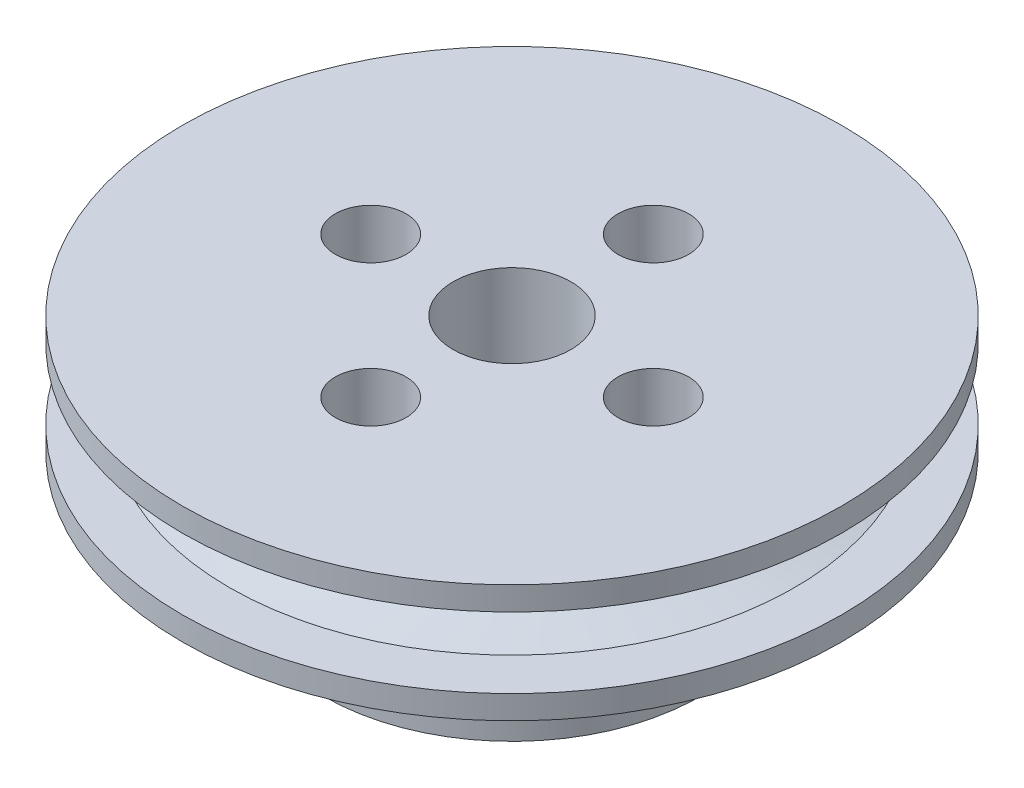
SolidWorks part; units mm, degrees
material "PET"
ref_plane "前视基准面" through (0, 0, 0) normal (0, 0, 1) x (1, 0, 0)
ref_plane "上视基准面" through (0, 0, 0) normal (0, 1, 0) x (1, 0, 0)
ref_plane "右视基准面" through (0, 0, 0) normal (1, 0, 0) x (0, 0, -1)
sketch "草图1" plane through (0, 0, 0) normal (0, 1, 0) x (1, 0, 0)
  circle A0 centre (0, 0) radius 8
  dimension "D1" = 16
extrude "凸台-拉伸1" add sketch "草图1" along normal blind 5
sketch "草图3" plane through (0, 0, 0) normal (0, 0, 1) x (1, 0, 0)
  line L0 (2.5, 5) -> (12, 5)
  line L1 (8, 5) -> (-8, 5) construction
  line L3 (12, 10) -> (2.5, 10)
  line L4 (0, 11) -> (0, 5) construction
  line L5 (12, 9) -> (12, 10)
  line L6 (12, 6) -> (12, 5)
  line L7 (2.5, 10) -> (2.5, 5)
  line L8 (12, 10) -> (14.0186, 10)
  line L9 (14.0186, 10) -> (14.0186, 9)
  line L10 (12, 9) -> (12, 6)
  line L11 (9, 7.5) -> (2.5, 7.5)
  spline S0 degree 4 poles (12.6644, 5.7868) (12.6335, 5.7968) (12.5806, 5.8139) (12.5498, 5.8242) (12.3125, 5.9004) (12.0321, 5.9899) (11.7628, 6.0752) (11.1308, 6.278) (10.8538, 6.3743) (10.4624, 6.5112) (10.3431, 6.5596) (10.1924, 6.6167) (10.1356, 6.6406) (10.0445, 6.6776) (9.9437, 6.7207) (9.8097, 6.7804) (9.6488, 6.8581) (9.471, 6.9535) (9.3035, 7.0608) (9.1707, 7.1685) (9.0813, 7.2708) (9.0343, 7.3491) (9.0097, 7.4144) (8.9991, 7.473) (8.9993, 7.5298) (9.0105, 7.5885) (9.0358, 7.654) (9.0837, 7.7325) (9.1547, 7.8126) (9.2439, 7.8908) (9.3633, 7.9775) (9.4804, 8.0499) (9.5998, 8.1154) (9.725, 8.1789) (9.8435, 8.2344) (9.962, 8.2881) (10.0939, 8.3423) (10.1801, 8.3786) (10.3472, 8.442) (10.4683, 8.4909) (10.8575, 8.627) (11.1337, 8.7229) (11.7644, 8.9253) (12.0322, 9.0101) (12.3131, 9.0998) (12.5493, 9.1756) (12.5808, 9.1861) (12.6336, 9.2032) (12.6643, 9.2132) knots 0 0 0 0 0 0.010416 0.020831 0.041663 0.083326 0.1552 0.227075 0.263013 0.29895 0.307934 0.316919 0.325903 0.334887 0.352856 0.370825 0.396081 0.421338 0.449866 0.466732 0.47811 0.486548 0.493647 0.500181 0.506692 0.513762 0.522298 0.533856 0.550816 0.565113 0.579411 0.604782 0.617467 0.630153 0.648061 0.665968 0.683876 0.692829 0.701783 0.737598 0.773414 0.845044 0.916674 0.958337 0.979169 0.989584 1 1 1 1 1 construction
  spline S1 degree 4 poles (12, 6) (11.8816, 6.0377) (11.6438, 6.1134) (11.1308, 6.278) (10.8538, 6.3743) (10.4624, 6.5112) (10.3431, 6.5596) (10.1924, 6.6167) (10.1356, 6.6406) (10.0445, 6.6776) (9.9437, 6.7207) (9.8097, 6.7804) (9.6488, 6.8581) (9.471, 6.9535) (9.3035, 7.0608) (9.1707, 7.1685) (9.0813, 7.2708) (9.0343, 7.3491) (9.0097, 7.4144) (8.9991, 7.473) (8.9993, 7.5298) (9.0105, 7.5885) (9.0358, 7.654) (9.0837, 7.7325) (9.1547, 7.8126) (9.2439, 7.8908) (9.3633, 7.9775) (9.4804, 8.0499) (9.5998, 8.1154) (9.725, 8.1789) (9.8435, 8.2344) (9.962, 8.2881) (10.0939, 8.3423) (10.1801, 8.3786) (10.3472, 8.442) (10.4683, 8.4909) (10.8575, 8.627) (11.1337, 8.7229) (11.6454, 8.8871) (11.882, 8.9624) (12, 9) knots 0.083326 0.083326 0.083326 0.083326 0.083326 0.1552 0.227075 0.263013 0.29895 0.307934 0.316919 0.325903 0.334887 0.352856 0.370825 0.396081 0.421338 0.449866 0.466732 0.47811 0.486548 0.493647 0.500181 0.506692 0.513762 0.522298 0.533856 0.550816 0.565113 0.579411 0.604782 0.617467 0.630153 0.648061 0.665968 0.683876 0.692829 0.701783 0.737598 0.773414 0.845044 0.916674 0.916674 0.916674 0.916674 0.916674
  point P4 (12, 9)
  point P7 (12, 6)
  dimension "D1" = 5
  dimension "D2" = 9.5
  dimension "D3" = 1
  dimension "D4" = 1
  dimension "D5" = 2.5
  dimension "D6" = 6.5
revolve "旋转3" add sketch "草图3" angle 360 about L4
sketch "草图4" plane through (0, 10, 0) normal (0, 1, 0) x (1, 0, 0)
  circle A0 centre (0, 0) radius 6 construction
  circle A1 centre (0, 6) radius 1.5
  circle A2 centre (6, 0) radius 1.5
  circle A3 centre (0, -6) radius 1.5
  circle A4 centre (-6, 0) radius 1.5
  point P14 (0, 0)
  dimension "D1" = 4
  dimension "D2" = 3
extrude "切除-拉伸1" cut sketch "草图4" against normal blind 5
sketch "草图5" plane through (0, 5, 0) normal (0, 1, 0) x (1, 0, 0)
  circle A0 centre (0, 6) radius 1.05
  circle A1 centre (-6, 0) radius 1.05
  circle A2 centre (6, 0) radius 1.05
  circle A3 centre (0, -6) radius 1.05
  dimension "D1" = 2.1
  dimension "D2" = 2.1
  dimension "D3" = 2.1
  dimension "D4" = 2.1
extrude "切除-拉伸2" cut sketch "草图5" against normal up to surface (5 mm away) up to face at (0, 0, 8)
sketch "草图6" plane through (0, 0, 0) normal (1, 0, 0) x (0, 0, -1)
  line L0 (-12, 9) -> (12, 6) construction
  line L1 (12, 6) -> (12, 9) construction
  line L2 (12, 9) -> (-12, 6) construction
  line L3 (-12, 6) -> (-12, 9) construction
  line L4 (0, 7.5) -> (-12, 7.5) construction
  circle A0 centre (-6, 7.5) radius 0.75
  spline S0 degree 4 poles (-12, 9) (-11.882, 8.9624) (-11.6454, 8.8871) (-11.1337, 8.7229) (-10.8575, 8.627) (-10.4683, 8.4909) (-10.3472, 8.442) (-10.1801, 8.3786) (-10.0939, 8.3423) (-9.962, 8.2881) (-9.8435, 8.2344) (-9.725, 8.1789) (-9.5998, 8.1154) (-9.4804, 8.0499) (-9.3633, 7.9775) (-9.2439, 7.8908) (-9.1547, 7.8126) (-9.0837, 7.7325) (-9.0358, 7.654) (-9.0105, 7.5885) (-8.9993, 7.5298) (-8.9991, 7.473) (-9.0097, 7.4144) (-9.0343, 7.3491) (-9.0813, 7.2708) (-9.1707, 7.1685) (-9.3035, 7.0608) (-9.471, 6.9535) (-9.6488, 6.8581) (-9.8097, 6.7804) (-9.9437, 6.7207) (-10.0445, 6.6776) (-10.1356, 6.6406) (-10.1924, 6.6167) (-10.3431, 6.5596) (-10.4624, 6.5112) (-10.8538, 6.3743) (-11.1308, 6.278) (-11.6438, 6.1134) (-11.8816, 6.0377) (-12, 6) knots 0.083326 0.083326 0.083326 0.083326 0.083326 0.154956 0.226586 0.262402 0.298217 0.307171 0.316124 0.334032 0.351939 0.369847 0.382533 0.395218 0.420589 0.434887 0.449184 0.466144 0.477702 0.486238 0.493308 0.499819 0.506353 0.513452 0.52189 0.533268 0.550134 0.578662 0.603919 0.629175 0.647144 0.665113 0.674097 0.683081 0.692066 0.70105 0.736987 0.772925 0.8448 0.916674 0.916674 0.916674 0.916674 0.916674 construction
  point P12 (-9, 7.5)
  dimension "D1" = 3
  dimension "D2" = 1.5
extrude "切除-拉伸3" cut sketch "草图6" against normal through all both and the other way through all
ref_axis "基准轴1" through (1.2472, 7.5, 6) along (1, 0, 0)
ref_plane "基准面1" through (0, 7.5, 0) normal (0, 1, 0) x (1, 0, 0)
ref_plane "基准面2" through (0, 0, 6) normal (0, 0, 1) x (1, 0, 0)
ref_plane "基准面3" through (0, 0, 9) normal (0, 0, 1) x (1, 0, 0)
ref_axis "切线" through (-13.2, 7.5, 9) along (1, 0, 0)
fillet "圆角1" radius 2 1 edges at (0, 5, 8) type face fillet first side face at (0, 5, 8) second side face at (0, 5, 8)
sketch "草图7" plane through (0, 5, 0) normal (0, 1, 0) x (1, 0, 0)
  circle A0 centre (0, 0) radius 2.5
  dimension "D1" = 5
extrude "切除-拉伸4" cut sketch "草图7" against normal through all
sketch "草图8" plane through (0, 0, 0) normal (0, 0, 1) x (1, 0, 0)
  line L0 (12, 10) -> (12, 9)
  line L1 (12, 9) -> (14, 9)
  line L2 (14, 9) -> (14, 10)
  line L3 (14, 10) -> (12, 10)
  line L4 (12, 6) -> (12, 5)
  line L5 (12, 5) -> (14, 5)
  line L6 (14, 5) -> (14, 6)
  line L7 (14, 6) -> (12, 6)
  line L8 (-12, 6) -> (12, 6) construction
  line L9 (-12, 9) -> (12, 9) construction
  line L10 (0, 9) -> (0, 6) construction
  dimension "D1" = 2
  dimension "D2" = 2
revolve "旋转4" add sketch "草图8" angle 360 about L10
